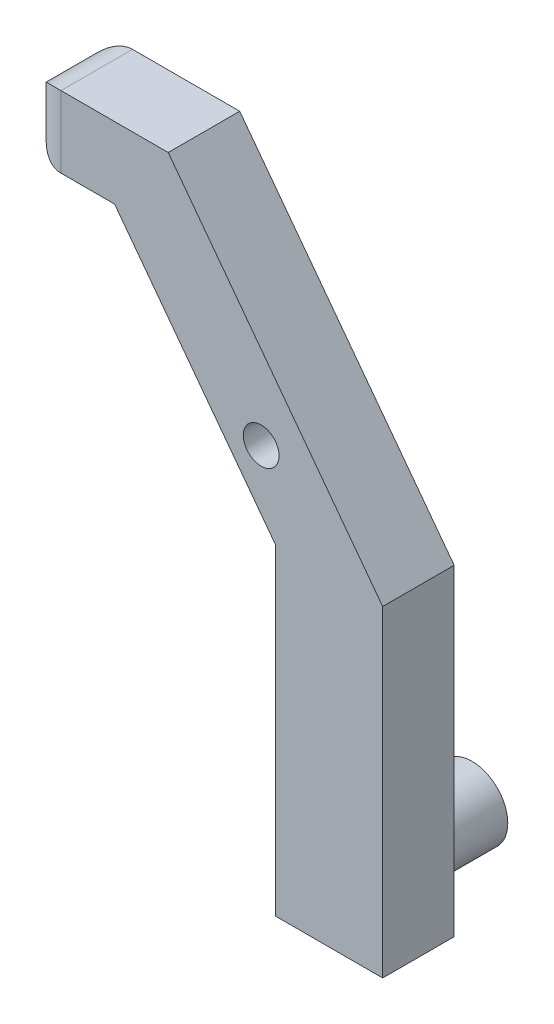
SolidWorks part; units mm, degrees
ref_plane "前视基准面" through (0, 0, 0) normal (0, 0, 1) x (1, 0, 0)
ref_plane "上视基准面" through (0, 0, 0) normal (0, 1, 0) x (1, 0, 0)
ref_plane "右视基准面" through (0, 0, 0) normal (1, 0, 0) x (0, 0, -1)
other "Configuration Table"
sketch "草图4" plane through (0, 0, 0) normal (0, 0, 1) x (1, 0, 0)
  line L0 (0, 0) -> (-30, 0)
  line L1 (-30, 0) -> (-30, 90)
  line L2 (-30, 90) -> (30, 170)
  line L3 (30, 170) -> (70, 170)
  line L4 (70, 170) -> (70, 150)
  line L5 (70, 150) -> (45, 150)
  line L6 (45, 150) -> (0, 90)
  line L7 (0, 90) -> (0, 0)
  point P3 (57.2015, 146.8612)
  point P10 (49.4294, 156.6318)
  point P11 (42.5456, 181.0583)
  point P12 (29.222, 172.1759)
  dimension "D1" = 90
  dimension "D2" = 30
  dimension "D3" = 90
  dimension "D4" = 100
  dimension "D5" = 75
  dimension "D6" = 20
  dimension "D7" = 70
extrude "凸台-拉伸1" add sketch "草图4" along normal blind 20
fillet "圆角2" radius 10 4 edges at (70, 150, 10) (70, 160, 0) (70, 170, 10) (70, 160, 20)
sketch "草图5" plane through (0, 0, 0) normal (0, 0, -1) x (-1, 0, 0)
  line L0 (30, 90) -> (30, 0) construction
  line L1 (0, 0) -> (30, 0)
  line L2 (0, 0) -> (0, 30)
  line L3 (0, 30) -> (30, 30)
  line L4 (30, 0) -> (30, 30)
  line L5 (0, 30) -> (30, 0) construction
  line L6 (30, 30) -> (0, 0)
  circle A0 centre (15, 15) radius 10
  point P10 (0, 30)
  dimension "D2" = 20
  dimension "D1" = 30
extrude "凸台-拉伸2" add sketch "草图5" along normal blind 20 contours L6 L5 A0 | L5 A0 L6 | L5 L6 A0 | A0 L5 L6 region at (-8.9979, 15, 0) region at (-15, 8.9979, 0) region at (-21.0021, 15, 0) region at (-15, 21.0021, 0)
sketch "草图6" plane through (0, 0, 20) normal (0, 0, 1) x (1, 0, 0)
  line L1 (0, 90) -> (45, 150) construction
  line L3 (0, 90) -> (-19.2, 104.4)
  line L4 (30, 170) -> (-30, 90) construction
  circle A0 centre (4, 112) radius 5
  dimension "D1" = 10
  dimension "D2" = 10
  dimension "D3" = 20
extrude "切除-拉伸1" cut sketch "草图6" against normal blind 20 contours A0 region at (4, 112, 20)
mirror "镜向3" about plane through (-30, 0, 20) normal (1, 0, 0) of "凸台-拉伸2", "切除-拉伸1", "圆角2", "凸台-拉伸1"
sketch "草图8" plane through (0, 0, 0) normal (0, -1, 0) x (1, 0, 0)
  line L0 (-60, 0) -> (0, 0) construction
  line L1 (0, 20) -> (-30, 20)
  line L2 (0, 20) -> (0, 0)
  line L3 (0, 0) -> (-30, 0)
  line L4 (-30, 20) -> (-30, 0)
  line L6 (-30, 20) -> (88.9762, 20)
  line L7 (-30, 20) -> (-30, -22.9764)
  line L8 (-30, -22.9764) -> (88.9762, -22.9764)
  line L9 (88.9762, 20) -> (88.9762, -22.9764)
  line M2 (-60, 0) -> (0, 0)
  line M3 (0, 0) -> (0, 20)
  line M4 (0, 20) -> (-60, 20)
extrude "切除-拉伸2" cut sketch "草图8" against normal through all contours L9 L6 L7 L8 M3 M2 | L4 M4 M2 M3 region at (-15, 0, 10) region at (35.4025, 0, -3.0155)
